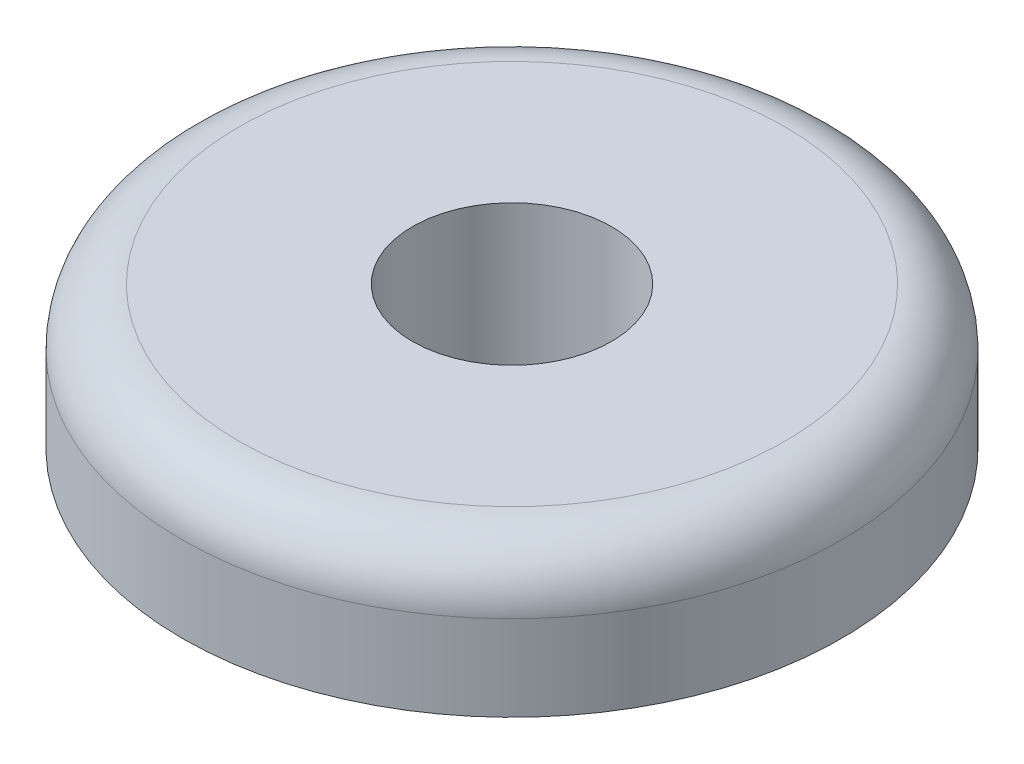
SolidWorks part; units mm, degrees
ref_plane "Front Plane" through (0, 0, 0) normal (0, 0, 1) x (1, 0, 0)
ref_plane "Top Plane" through (0, 0, 0) normal (0, 1, 0) x (1, 0, 0)
ref_plane "Right Plane" through (0, 0, 0) normal (1, 0, 0) x (0, 0, -1)
sketch "Sketch1" plane through (0, 0, 0) normal (0, 1, 0) x (1, 0, 0)
  circle A0 centre (0, 0) radius 14 construction
  circle A1 centre (0, 0) radius 3.5
  circle A2 centre (0, 0) radius 11.587
  dimension "D1" = 28
  dimension "D2" = 2.413
  dimension "D3" = 7
extrude "Boss-Extrude1" add sketch "Sketch1" along normal blind 5
fillet "Fillet1" radius 2 1 edges at (0, 5, 11.587)
